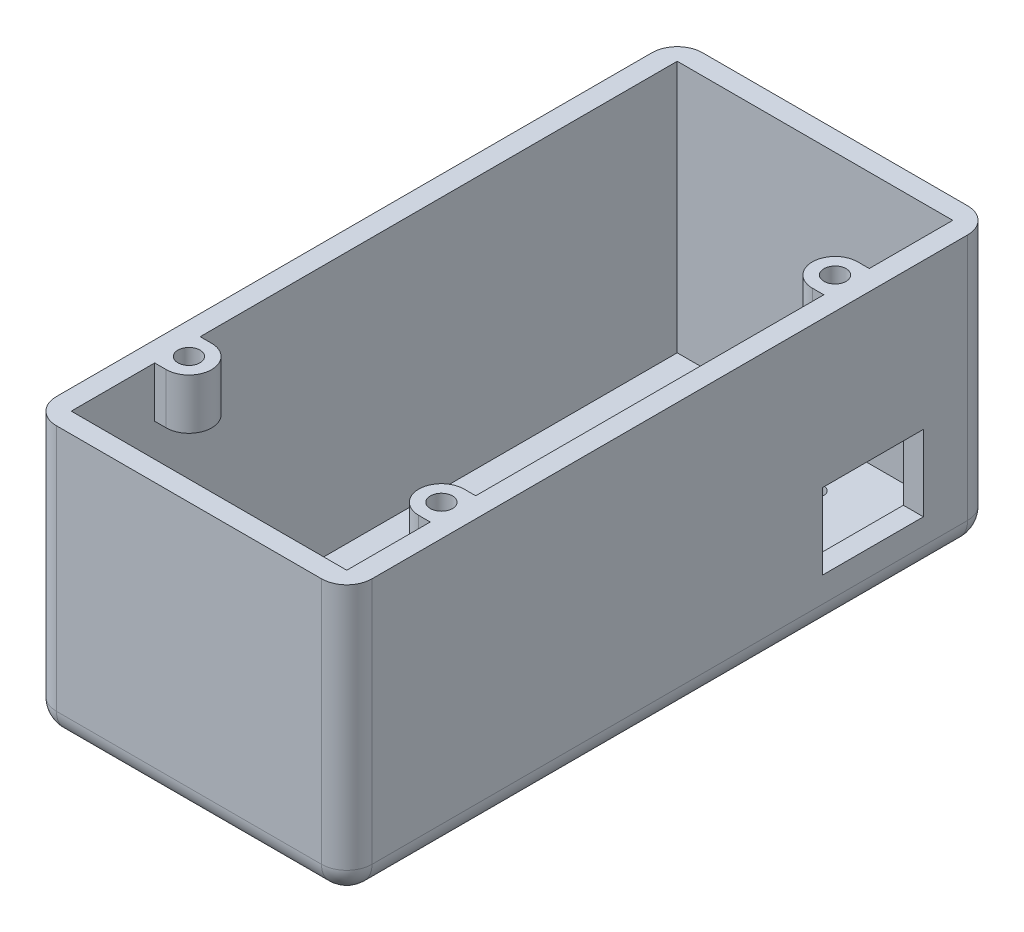
SolidWorks part; units mm, degrees
ref_plane "Front Plane" through (0, 0, 0) normal (0, 0, 1) x (1, 0, 0)
ref_plane "Top Plane" through (0, 0, 0) normal (0, 1, 0) x (1, 0, 0)
ref_plane "Right Plane" through (0, 0, 0) normal (1, 0, 0) x (0, 0, -1)
sketch "Sketch1" plane through (0, 0, 0) normal (0, 1, 0) x (1, 0, 0)
  line L1 (-25, 51.175) -> (25, 51.175)
  line L2 (-25, 51.175) -> (-25, -51.175)
  line L3 (-25, -51.175) -> (25, -51.175)
  line L4 (25, 51.175) -> (25, -51.175)
  line L5 (-25, 51.175) -> (25, -51.175) construction
  line L6 (-25, -51.175) -> (25, 51.175) construction
  line L7 (-21.825, 48) -> (21.825, 48)
  line L8 (-21.825, 48) -> (-21.825, -48)
  line L9 (-21.825, -48) -> (21.825, -48)
  line L10 (21.825, 48) -> (21.825, -48)
  line L11 (-21.825, 48) -> (21.825, -48) construction
  line L12 (-21.825, -48) -> (21.825, 48) construction
  point P0 (0, 0)
  point P6 (0, 0)
  dimension "D1" = 3.175
  dimension "D2" = 3.175
  dimension "D3" = 102.35
  dimension "D4" = 50
extrude "Boss-Extrude1" add sketch "Sketch1" along normal blind 40
sketch "Sketch2" plane through (0, 0, 0) normal (0, -1, 0) x (1, 0, 0)
  line L1 (25, -51.175) -> (-25, -51.175)
  line L2 (25, -51.175) -> (25, 51.175)
  line L3 (25, 51.175) -> (-25, 51.175)
  line L4 (-25, -51.175) -> (-25, 51.175)
extrude "Boss-Extrude2" add sketch "Sketch2" along normal blind 3.175
fillet "Fillet1" radius 4 8 edges at (25, 18.4125, 51.175) (25, 18.4125, -51.175) (-25, 18.4125, -51.175) (-25, 18.4125, 51.175) (0, -3.175, 51.175) (-25, -3.175, 0) (0, -3.175, -51.175) (25, -3.175, 0)
sketch "Sketch3" plane through (0, 0, 0) normal (0, 1, 0) x (1, 0, 0)
  line L0 (-21.825, -48) -> (21.825, -48) construction
  line L1 (-15, 40.05) -> (8.05, 40.05) construction
  line L2 (-15, 40.05) -> (-15, -18) construction
  line L3 (-15, -18) -> (8.05, -18) construction
  line L4 (8.05, 40.05) -> (8.05, -18) construction
  line L6 (-21, -47.175) -> (-21, 47.175) construction
  circle A0 centre (-15, 40.05) radius 1.3
  circle A1 centre (8.05, 40.05) radius 1.3
  circle A2 centre (8.05, -18) radius 1.3
  circle A3 centre (-15, -18) radius 1.3
  dimension "D2" = 2.6
  dimension "D1" = 58.05
  dimension "D3" = 23.05
  dimension "D4" = 30
  dimension "D5" = 6
extrude "Cut-Extrude1" cut sketch "Sketch3" against normal up to surface (3.175 mm away) up to face at (0, -3.175, 0)
sketch "Sketch4" plane through (0, 40, 0) normal (0, 1, 0) x (1, 0, 0)
  line L0 (-20, -27.575) -> (-21.825, -27.575)
  line L1 (-21.825, 48) -> (-21.825, -48) construction
  line L2 (-21.825, -27.575) -> (-21.825, -34.775)
  line L3 (-21.825, -34.775) -> (-20, -34.775)
  line L4 (0, -51.175) -> (0, 51.175) construction
  line L5 (-21, -51.175) -> (21, -51.175) construction
  line L6 (21, 51.175) -> (-21, 51.175) construction
  line L7 (-25, 47.175) -> (-25, -47.175) construction
  line L8 (21.825, -34.775) -> (20, -34.775)
  line L9 (21.825, -27.575) -> (21.825, -34.775)
  line L10 (20, -27.575) -> (21.825, -27.575)
  line L11 (-25, 0) -> (25, 0) construction
  line L12 (25, -47.175) -> (25, 47.175) construction
  line L13 (20, 27.575) -> (21.825, 27.575)
  line L14 (21.825, 27.575) -> (21.825, 34.775)
  line L15 (21.825, 34.775) -> (20, 34.775)
  arc A0 (-20, -34.775) -> (-20, -27.575) centre (-20, -31.175) ccw
  arc A1 (20, -34.775) -> (20, -27.575) centre (20, -31.175) cw
  arc A2 (20, 34.775) -> (20, 27.575) centre (20, 31.175) ccw
  dimension "D1" = 7.2
  dimension "D2" = 5
  dimension "D3" = 20
extrude "Boss-Extrude3" add sketch "Sketch4" against normal blind 8
sketch "Sketch5" plane through (0, 40, 0) normal (0, 1, 0) x (1, 0, 0)
  line L0 (0, 51.175) -> (0, -51.175) construction
  line L1 (21, 51.175) -> (-21, 51.175) construction
  line L2 (-21, -51.175) -> (21, -51.175) construction
  line L3 (-25, 0) -> (25, 0) construction
  line L4 (-25, 47.175) -> (-25, -47.175) construction
  line L5 (25, -47.175) -> (25, 47.175) construction
  circle A0 centre (-20, -31.175) radius 1.75
  circle A1 centre (20, -31.175) radius 1.75
  circle A2 centre (20, 31.175) radius 1.75
  dimension "D1" = 3.5
extrude "Cut-Extrude2" cut sketch "Sketch5" against normal blind 5
sketch "Sketch6" plane through (25, 0, 0) normal (1, 0, 0) x (0, 0, -1)
  line L0 (-47.175, 0.825) -> (47.175, 0.825) construction
  line L1 (40.175, 4.825) -> (24.175, 4.825)
  line L2 (40.175, 4.825) -> (40.175, 16.825)
  line L3 (40.175, 16.825) -> (24.175, 16.825)
  line L4 (24.175, 4.825) -> (24.175, 16.825)
  line L5 (47.175, 0.825) -> (47.175, 40) construction
  dimension "D1" = 4
  dimension "D2" = 7
  dimension "D3" = 12
  dimension "D4" = 16
extrude "Cut-Extrude3" cut sketch "Sketch6" against normal blind 10
